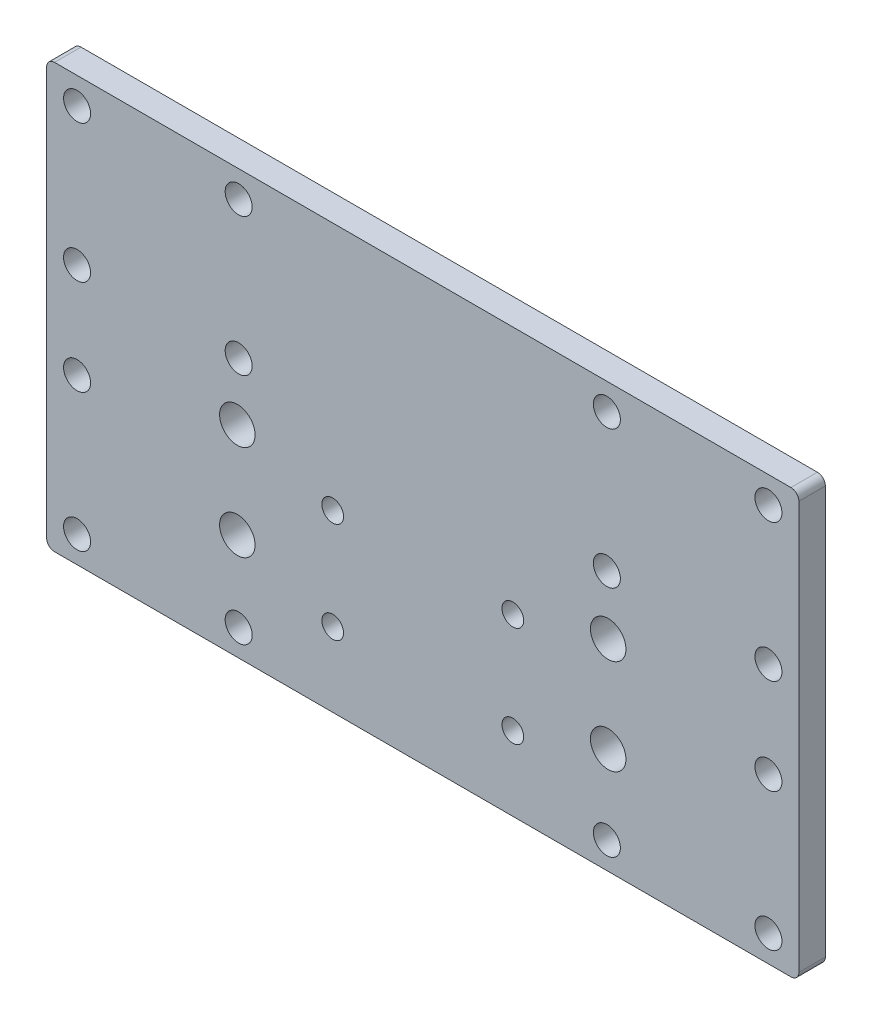
SolidWorks part; units mm, degrees
ref_plane "Front Plane" through (0, 0, 0) normal (0, 0, 1) x (1, 0, 0)
ref_plane "Top Plane" through (0, 0, 0) normal (0, 1, 0) x (1, 0, 0)
ref_plane "Right Plane" through (0, 0, 0) normal (1, 0, 0) x (0, 0, -1)
sketch "Sketch1" plane through (0, 0, 0) normal (0, 0, 1) x (1, 0, 0)
  line L1 (-71, -40) -> (71, -40)
  line L2 (-71, -40) -> (-71, 40)
  line L3 (-71, 40) -> (71, 40)
  line L4 (71, -40) -> (71, 40)
  line L5 (-71, -40) -> (71, 40) construction
  line L6 (-71, 40) -> (71, -40) construction
  point P0 (0, 0)
  dimension "D1" = 80
  dimension "D2" = 142
extrude "Boss-Extrude1" add sketch "Sketch1" along normal mid plane 5
sketch "Sketch2" plane through (0, 0, 2.5) normal (0, 0, 1) x (1, 0, 0)
  line L3 (-65.25, 40) -> (-65.25, -40)
  line L4 (-65.25, 40) -> (-65.25, -40) construction
  line L6 (65.25, -40) -> (65.25, 40)
  line L7 (65.25, -40) -> (65.25, 40) construction
  line L13 (-34.75, 40) -> (-34.75, -40)
  line L14 (-34.75, 40) -> (-34.75, -40) construction
  line L16 (34.75, -40) -> (34.75, 40)
  line L18 (34.75, -40) -> (34.75, 40) construction
  line L20 (71, 35) -> (-71, 35)
  line L21 (71, 35) -> (-71, 35) construction
  line L23 (-71, -35) -> (71, -35)
  line L24 (-71, -35) -> (71, -35) construction
  line L26 (71, 9) -> (-71, 9)
  line L27 (71, 9) -> (-71, 9) construction
  line L29 (-71, -9) -> (71, -9)
  line L30 (-71, -9) -> (71, -9) construction
  circle A0 centre (-65.25, 35) radius 2.55
  circle A1 centre (-34.75, 35) radius 2.55
  circle A2 centre (-34.75, 9) radius 2.55
  circle A3 centre (-65.25, 9) radius 2.55
  circle A4 centre (65.25, 35) radius 2.55
  circle A5 centre (65.25, 9) radius 2.55
  circle A6 centre (34.75, 9) radius 2.55
  circle A7 centre (34.75, 35) radius 2.55
  circle A8 centre (-65.25, -9) radius 2.55
  circle A10 centre (-34.75, -35) radius 2.55
  circle A11 centre (-65.25, -35) radius 2.55
  circle A13 centre (65.25, -9) radius 2.55
  circle A14 centre (65.25, -35) radius 2.55
  circle A15 centre (34.75, -35) radius 2.55
  dimension "D9" = 5.1
  dimension "D10" = 5.1
  dimension "D11" = 5.1
  dimension "D12" = 5.1
  dimension "D13" = 5.1
  dimension "D14" = 5.1
  dimension "D15" = 5.1
  dimension "D16" = 5.1
  dimension "D17" = 5.1
  dimension "D18" = 5.1
  dimension "D20" = 5.1
  dimension "D21" = 5.1
  dimension "D23" = 5.1
  dimension "D24" = 5.1
  dimension "D1" = 5.75
  dimension "D2" = 5.75
  dimension "D3" = 36.25
  dimension "D4" = 36.25
  dimension "D5" = 5
  dimension "D6" = 5
  dimension "D7" = 31
  dimension "D8" = 31
extrude "Cut-Extrude1" cut sketch "Sketch2" against normal through all
sketch "Sketch3" plane through (0, 0, 2.5) normal (0, 0, 1) x (1, 0, 0)
  line L0 (-71, -40) -> (71, -40) construction
  line L1 (-17, -7) -> (17, -7) construction
  line L2 (-17, -7) -> (-17, -26) construction
  line L3 (-17, -26) -> (17, -26) construction
  line L4 (17, -7) -> (17, -26) construction
  line L5 (-17, -7) -> (17, -26) construction
  line L6 (-17, -26) -> (17, -7) construction
  line L7 (0, 40) -> (0, -40) construction
  line L8 (71, 40) -> (-71, 40) construction
  circle A0 centre (-17, -7) radius 2.05
  circle A1 centre (-17, -26) radius 2.05
  circle A2 centre (17, -26) radius 2.05
  circle A3 centre (17, -7) radius 2.05
  point P0 (0, 0)
  dimension "D3" = 4.1
  dimension "D4" = 4.1
  dimension "D5" = 4.1
  dimension "D6" = 4.1
  dimension "D1" = 34
  dimension "D2" = 19
  dimension "D7" = 14
  dimension "D8" = 17
extrude "Cut-Extrude2" cut sketch "Sketch3" against normal through all
sketch "Sketch4" plane through (0, 0, 2.5) normal (0, 0, 1) x (1, 0, 0)
  line L0 (0, 40) -> (0, -40) construction
  line L1 (-35, -20) -> (35, -20) construction
  line L2 (-35, -20) -> (-35, -2) construction
  line L3 (-35, -2) -> (35, -2) construction
  line L4 (35, -20) -> (35, -2) construction
  line L5 (-35, -20) -> (35, -2) construction
  line L6 (-35, -2) -> (35, -20) construction
  line L7 (71, 40) -> (-71, 40) construction
  line L8 (-71, -40) -> (71, -40) construction
  circle A0 centre (-35, -2) radius 3.35
  circle A1 centre (35, -2) radius 3.35
  circle A2 centre (35, -20) radius 3.35
  circle A3 centre (-35, -20) radius 3.35
  point P0 (0, -11)
  dimension "D3" = 6.7
  dimension "D4" = 6.7
  dimension "D5" = 6.7
  dimension "D6" = 6.7
  dimension "D1" = 70
  dimension "D2" = 18
  dimension "D7" = 20
extrude "Cut-Extrude3" cut sketch "Sketch4" against normal through all
fillet "Fillet1" radius 1.5 4 edges at (-71, -40, 0) (71, -40, 0) (71, 40, 0) (-71, 40, 0)
equation "\"D4@Sketch3\"=\"D3@Sketch3\""
equation "\"D5@Sketch3\"=\"D3@Sketch3\""
equation "\"D6@Sketch3\"=\"D3@Sketch3\""
equation "\"D4@Sketch4\"=\"D3@Sketch4\""
equation "\"D5@Sketch4\"=\"D3@Sketch4\""
equation "\"D6@Sketch4\"=\"D3@Sketch4\""
equation "\"D10@Sketch2\"=\"D24@Sketch2\""
equation "\"D16@Sketch2\"=\"D24@Sketch2\""
